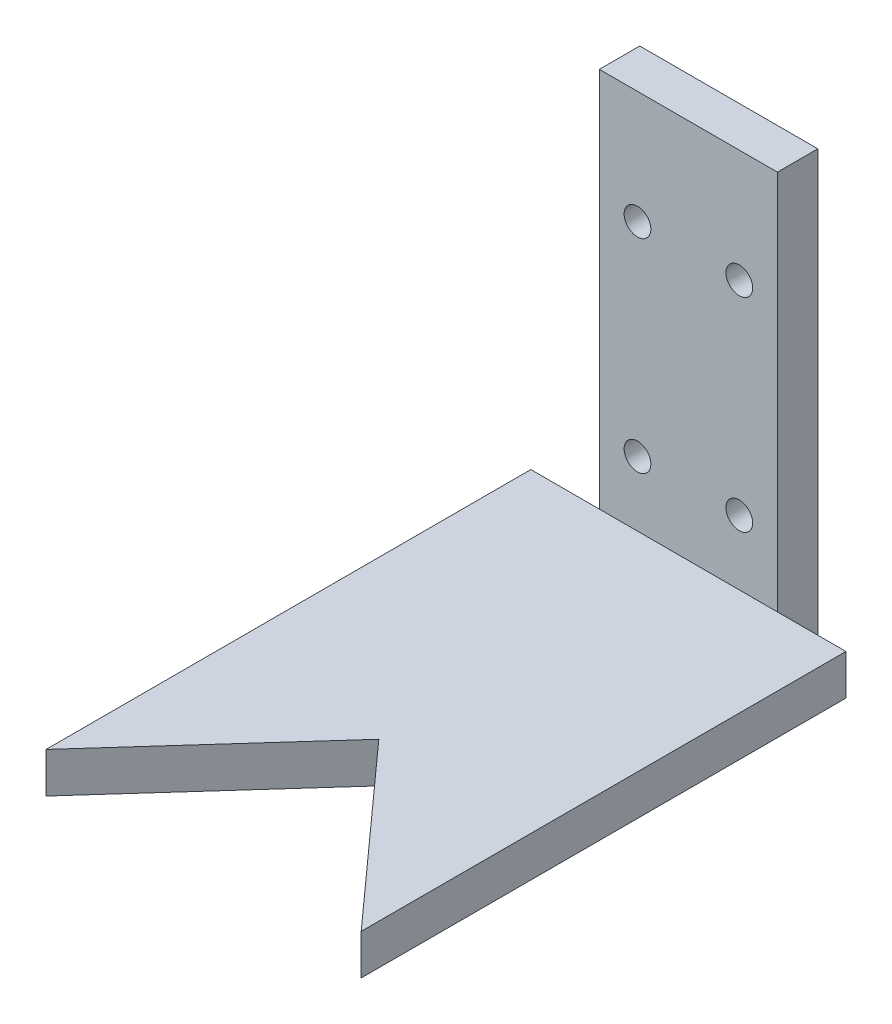
SolidWorks part; units mm, degrees
ref_plane "Front" through (0, 0, 0) normal (0, 0, 1) x (1, 0, 0)
ref_plane "Top" through (0, 0, 0) normal (0, 1, 0) x (1, 0, 0)
ref_plane "Right" through (0, 0, 0) normal (1, 0, 0) x (0, 0, -1)
sketch "Sketch1" plane through (0, 0, 0) normal (0, 0, 1) x (1, 0, 0)
  line L1 (0, 0) -> (27.9908, 0)
  line L2 (0, 0) -> (0, 66.2178)
  line L3 (0, 66.2178) -> (27.9908, 66.2178)
  line L4 (27.9908, 0) -> (27.9908, 66.2178)
  dimension "D1" = 27.9908
  dimension "D2" = 66.2178
extrude "Boss-Extrude1" add sketch "Sketch1" along normal blind 6.35
sketch "Sketch4" plane through (0, 0, 6.35) normal (0, 0, 1) x (1, 0, 0)
  line L0 (13.9954, 66.2178) -> (13.9954, -53.5178) construction
  line L1 (-10.7696, 0) -> (38.7604, 0)
  line L2 (-10.7696, 0) -> (-10.7696, 6.35)
  line L3 (-10.7696, 6.35) -> (38.7604, 6.35)
  line L4 (38.7604, 0) -> (38.7604, 6.35)
  line L6 (27.9908, 66.2178) -> (0, 66.2178) construction
  point P8 (13.9954, 6.35)
  point P9 (14.6194, 66.2178)
  dimension "D1" = 49.53
  dimension "D2" = 6.35
extrude "Boss-Extrude3" add sketch "Sketch4" along normal blind 76.2
sketch "Sketch5" plane through (0, 6.35, 0) normal (0, 1, 0) x (1, 0, 0)
  line L0 (38.7604, -82.55) -> (-10.7696, -82.55) construction
  line L1 (-10.7696, -82.55) -> (-10.7696, -6.35) construction
  line L2 (-10.7696, -82.55) -> (13.9954, -55.0096)
  line L3 (13.9954, -55.0096) -> (38.7604, -82.55)
  line L4 (38.7604, -82.55) -> (-10.7696, -82.55)
  circle A1 centre (13.9954, -71.755) radius 11.1967
  dimension "D2" = 10.795
  dimension "D3" = 24.765
extrude "Cut-Extrude1" cut sketch "Sketch5" against normal through all contours L3 L4 L2
sketch "Sketch6" plane through (0, 6.35, 0) normal (0, 1, 0) x (1, 0, 0)
hole_wizard "M5x0.8 Tapped Hole1" positions "Sketch7" profile "Sketch8" tap size "M5x0.8" standard "ANSI Metric" end condition through all
sketch "Sketch7" plane through (0, 0, 0) normal (0, 0, -1) x (-1, 0, 0)
  line L0 (-27.9908, 66.2178) -> (0, 66.2178) construction
  line L1 (0, 0) -> (-27.9908, 0) construction
  line L2 (0, 66.2178) -> (0, 0) construction
  line L3 (-27.9908, 0) -> (-27.9908, 66.2178) construction
  point P0 (-21.9964, 48.4886)
  point P2 (-5.9944, 48.4886)
  point P4 (-5.9944, 16.51)
  point P6 (-21.9964, 16.51)
  dimension "D1" = 17.7292
  dimension "D2" = 17.7292
  dimension "D3" = 16.51
  dimension "D4" = 16.51
  dimension "D5" = 5.9944
  dimension "D6" = 5.9944
  dimension "D7" = 5.9944
  dimension "D8" = 5.9944
sketch "Sketch8" plane through (21.9964, 48.4886, 0) normal (1, 0, 0) x (0, 1, 0)
  line L0 (0, 0) -> (0, 82.55)
  line L1 (0, 82.55) -> (2.1, 82.55)
  line L2 (2.1, 82.55) -> (2.1, 0)
  line L5 (2.1, 0) -> (0, 0)
  line L11 (0, -6.35) -> (0, 107.95) construction
  dimension "Thru Tap Drill Dia." = 4.2
  dimension "Thru Tap Drill Depth" = 82.55
